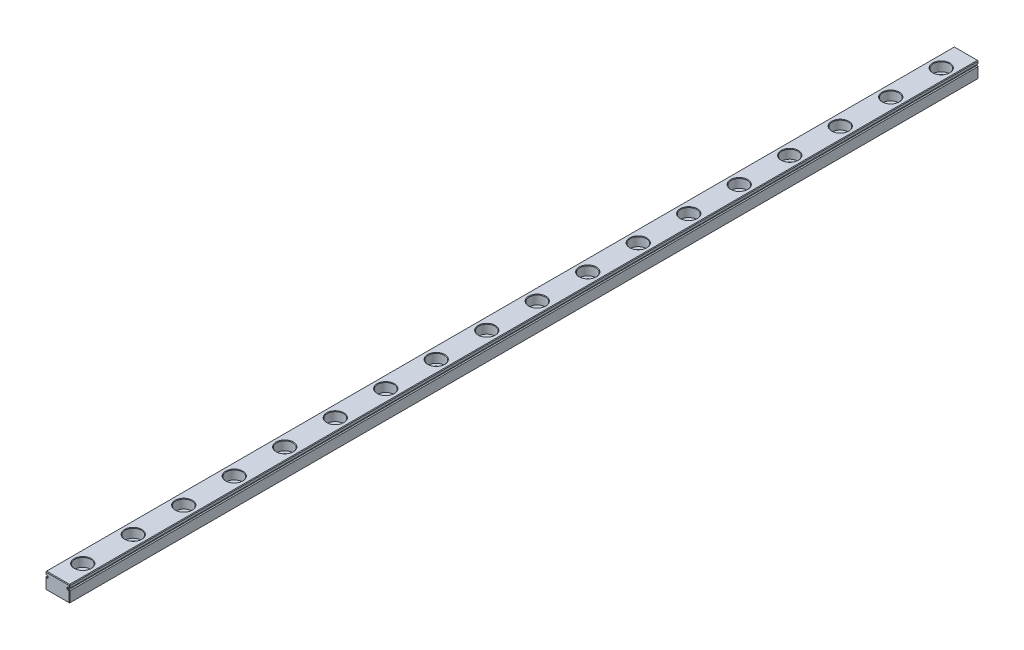
SolidWorks part; units mm, degrees
material "AISI 304"
ref_plane "Front Plane" through (0, 0, 0) normal (0, 0, 1) x (1, 0, 0)
ref_plane "Top Plane" through (0, 0, 0) normal (0, 1, 0) x (1, 0, 0)
ref_plane "Right Plane" through (0, 0, 0) normal (1, 0, 0) x (0, 0, -1)
sketch "Sketch1" plane through (0, 0, 0) normal (0, 0, 1) x (1, 0, 0)
  line L0 (0, 0) -> (0, 8) construction
  line L1 (0, 8) -> (12, 8)
  line L2 (0, 0) -> (12, 0)
  line L3 (0, 8) -> (0, 6.75)
  line L4 (0, 6.75) -> (0.5, 6.25) construction
  line L5 (0.5, 6.25) -> (1, 6.25)
  line L6 (0.5, 5.75) -> (0, 5.25) construction
  line L7 (0, 5.25) -> (0, 0)
  line L8 (1, 6.25) -> (1, 5.75)
  line L9 (1, 5.75) -> (0.5, 5.75)
  line L10 (0.5, 5.75) -> (0.75, 6) construction
  line L11 (0.75, 6) -> (0.5, 6.25) construction
  line L12 (0, 6.75) -> (0, 6.559)
  line L13 (0, 5.25) -> (0, 5.441)
  line L14 (6, 8) -> (6, 0) construction
  line L15 (11.25, 6) -> (11.5, 6.25) construction
  line L16 (11.5, 5.75) -> (11.25, 6) construction
  line L17 (11.5, 5.75) -> (12, 5.25) construction
  line L18 (12, 6.75) -> (11.5, 6.25) construction
  line L19 (12, 0) -> (12, 8) construction
  line L20 (12, 5.25) -> (12, 5.441)
  line L21 (12, 6.75) -> (12, 6.559)
  line L22 (11, 5.75) -> (11.5, 5.75)
  line L23 (11, 6.25) -> (11, 5.75)
  line L24 (12, 5.25) -> (12, 0)
  line L25 (11.5, 6.25) -> (11, 6.25)
  line L26 (12, 8) -> (12, 6.75)
  arc A0 (0, 5.441) -> (0.5, 5.75) centre (0, 6) ccw
  arc A1 (0.5, 6.25) -> (0, 6.559) centre (0, 6) ccw
  arc A2 (11.5, 6.25) -> (12, 6.559) centre (12, 6) cw
  arc A3 (12, 5.441) -> (11.5, 5.75) centre (12, 6) cw
  point P4 (1, 6)
  point P28 (11, 6)
  dimension "D1" = 8
  dimension "D2" = 6
  dimension "D3" = 0.5
  dimension "D4" = 45
  dimension "D5" = 2
  dimension "D6" = 1
extrude "Boss-Extrude1" add sketch "Sketch1" along normal blind 450
chamfer "Chamfer1" distance 0.3 angle 45 36 edges at (0, 0, 225) (12, 0, 225) (0, 8, 225) (12, 8, 225) (0.2939, 5.5245, 450) (0.75, 5.75, 450) (1, 6, 450) (0.75, 6.25, 450) (0.2939, 6.4755, 450) (0, 7.2795, 450) (6, 8, 450) (12, 7.2795, 450) (11.7061, 6.4755, 450) (11.25, 6.25, 450) (11, 6, 450) (11.25, 5.75, 450) (11.7061, 5.5245, 450) (12, 2.7205, 450) (6, 0, 450) (0, 2.7205, 450) (12, 2.7205, 0) (11.7061, 5.5245, 0) (11.25, 5.75, 0) (11, 6, 0) (11.25, 6.25, 0) (11.7061, 6.4755, 0) (12, 7.2795, 0) (6, 0, 0) (0, 2.7205, 0) (0.2939, 5.5245, 0) (0.75, 5.75, 0) (1, 6, 0) (0.75, 6.25, 0) (0.2939, 6.4755, 0) (0, 7.2795, 0) (6, 8, 0)
hole_wizard "CBORE for M5 Hex Head Bolt1" positions "3DSketch1" profile "Sketch3" counterbore size "M5" standard "ANSI Metric" end condition through all
sketch3d "3DSketch1"
  line L0 (6, 8, 0) -> (6, 8, 12.5) construction
  line L1 (11.7, 8, 0) -> (0.3, 8, 0) construction
  point P0 (6, 8, 12.5)
  dimension "D1" = 12.5
sketch "Sketch3" plane through (6, 8, 12.5) normal (1, 0, 0) x (0, 0, 1)
  line L0 (0, 0) -> (0, 8)
  line L1 (2.25, 7.75) -> (2.5, 8)
  line L2 (4, 4.5) -> (2.25, 4.5)
  line L3 (2.25, 4.5) -> (2.25, 7.75)
  line L5 (4, 4.5) -> (4, 0.25)
  line L6 (4, 0.25) -> (4.25, 0)
  line L7 (4.25, 0) -> (0, 0)
  line L8 (-4, 0.25) -> (-4.25, 0) construction
  line L11 (0, -6.35) -> (0, 107.95) construction
  line L12 (2.5, 8) -> (0, 8)
  line L13 (-2.25, 7.75) -> (-2.5, 8) construction
  dimension "Thru Hole Dia." = 4.5
  dimension "Thru Hole Depth" = 8
  dimension "C'Bore Dia." = 8
  dimension "C'Bore Depth" = 4.5
  dimension "Near C'Sink Dia." = 8.5
  dimension "Near C'Sink Angle" = 90
  dimension "Far C'Sink Dia." = 5
  dimension "Far C'Sink Angle" = 90
pattern_linear "LPattern1" count 18 spacing 25 along (0, 0, 1) of "CBORE for M5 Hex Head Bolt1"
